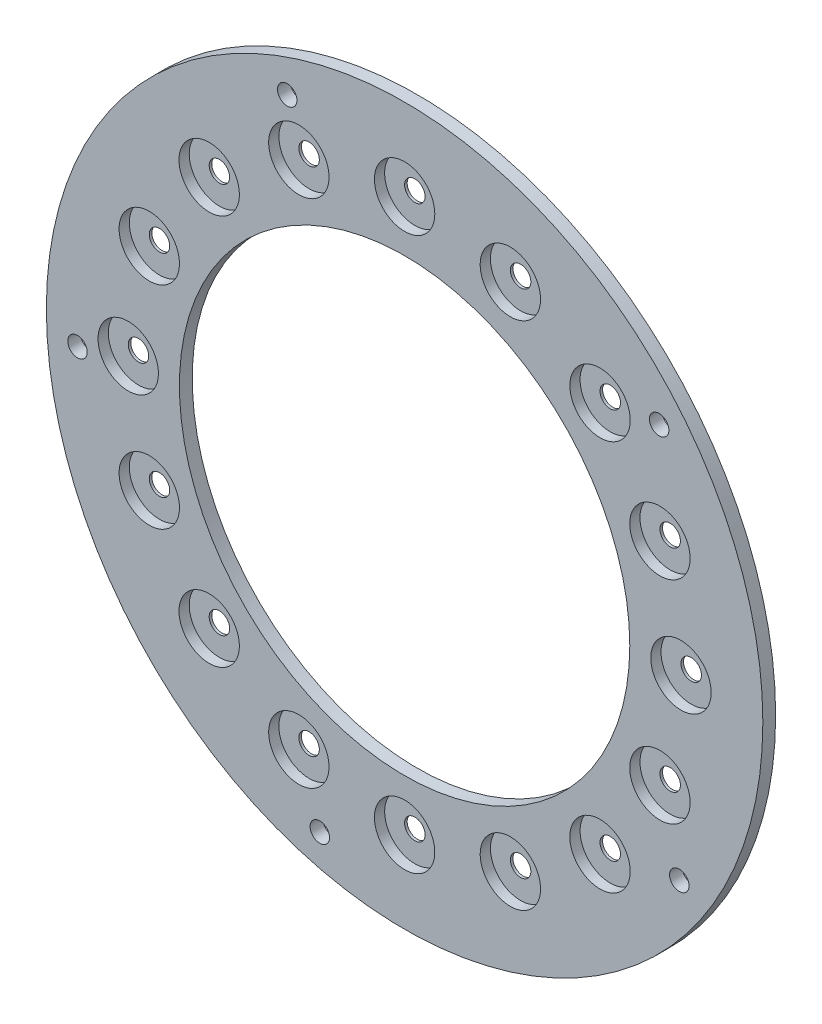
SolidWorks part; units mm, degrees
ref_plane "Front Plane" through (0, 0, 0) normal (0, 0, 1) x (1, 0, 0)
ref_plane "Top Plane" through (0, 0, 0) normal (0, 1, 0) x (1, 0, 0)
ref_plane "Right Plane" through (0, 0, 0) normal (1, 0, 0) x (0, 0, -1)
ref_axis "X-Axis" through (-88.99, 0, 0) along (1, 0, 0)
ref_axis "Y-Axis" through (0, 55, 0) along (0, -1, 0)
ref_axis "Z-Axis" through (0, 0, -88.99) along (0, 0, 1)
sketch "Sketch1" plane through (0, 0, 0) normal (0, 0, 1) x (1, 0, 0)
  circle A0 centre (0, 0) radius 35
  dimension "D1" = 70
extrude "Boss-Extrude1" add sketch "Sketch1" along normal blind 1.55
sketch "Sketch2" plane through (0, 0, 1.55) normal (0, 0, 1) x (1, 0, 0)
  circle A0 centre (0, 0) radius 22
  dimension "D1" = 44
extrude "Cut-Extrude1" cut sketch "Sketch2" against normal through all
sketch "Sketch3" plane through (0, 0, 1.55) normal (0, 0, 1) x (1, 0, 0)
  line L0 (0, 0) -> (0, 27) construction
  circle A0 centre (0, 27) radius 2.95
  dimension "D1" = 5.9
  dimension "D2" = 27
extrude "Cut-Extrude6" cut sketch "Sketch3" against normal blind 1
sketch "Sketch5" plane through (0, 0, 1.55) normal (0, 0, 1) x (1, 0, 0)
  circle A0 centre (0, 27) radius 1
  dimension "D1" = 2
extrude "Cut-Extrude7" cut sketch "Sketch5" against normal through all
other "Move Face1" flip direction yes face at (1, 27, 0) offset 0.3 parameters "D1"=0.3
pattern_circular "CirPattern2" count 16 over 360 about axis through (0, 0, -88.99) along (0, 0, 1) of "Cut-Extrude6", "Cut-Extrude7"
sketch "Sketch6" plane through (0, 0, 0.3) normal (0, 0, -1) x (-1, 0, 0)
  line L0 (0, 0) -> (0, 35) construction
  line L1 (0, 0) -> (11.4678, 29.8746) construction
  circle A0 centre (0, 0) radius 35 construction
  circle A1 centre (11.4678, 29.8746) radius 0.95
  dimension "D2" = 1.9
  dimension "D1" = 32
  dimension "D3" = 21
extrude "Cut-Extrude8" cut sketch "Sketch6" against normal through all
pattern_circular "CirPattern3" count 5 over 360 about axis through (0, 0, -88.99) along (0, 0, 1) of "Cut-Extrude8"
